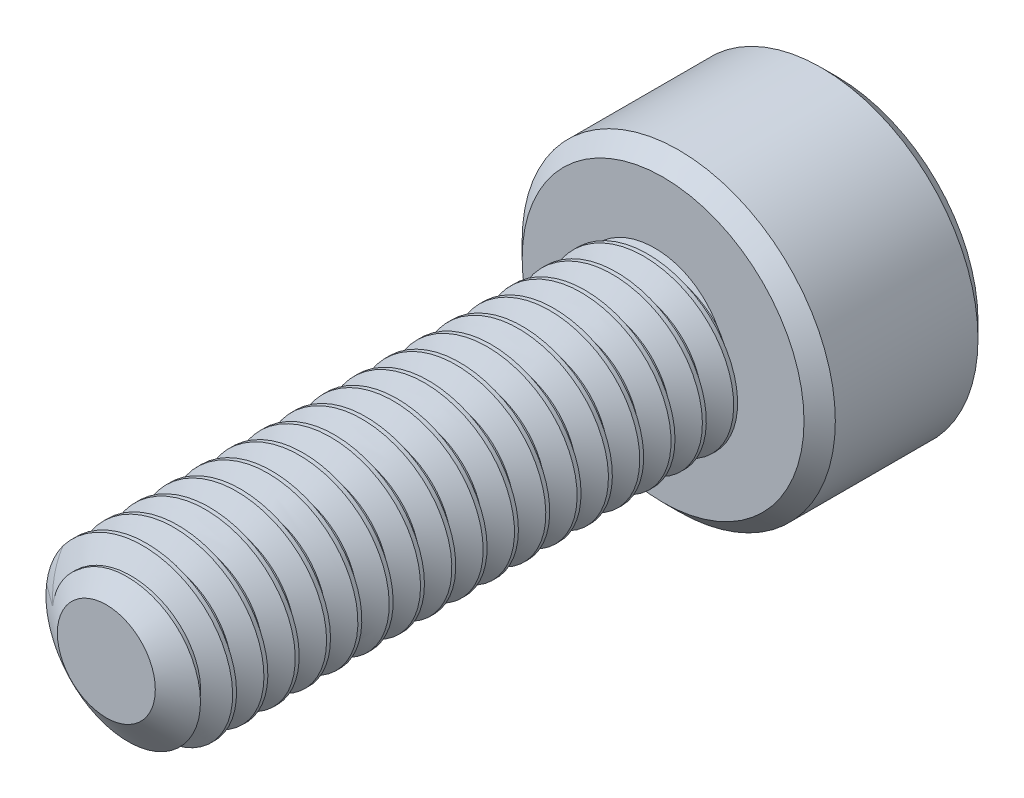
SolidWorks part; units mm, degrees
ref_plane "Front Plane" through (0, 0, 0) normal (0, 0, 1) x (1, 0, 0)
ref_plane "Top Plane" through (0, 0, 0) normal (0, 1, 0) x (1, 0, 0)
ref_plane "Right Plane" through (0, 0, 0) normal (1, 0, 0) x (0, 0, -1)
sketch "Sketch1" plane through (0, 0, 0) normal (0, 0, 1) x (1, 0, 0)
  circle A0 centre (0, 0) radius 1.25
  dimension "OD" = 2.5
extrude "Extrude1" add sketch "Sketch1" against normal blind 8
sketch "Sketch2" plane through (0, 0, 0) normal (0, 0, 1) x (1, 0, 0)
  circle A0 centre (0, 0) radius 1.25 construction
  circle A1 centre (0, 0) radius 1.25
curve "Helix/Spiral1" pitch 0.45 height 8.45 radius 1.25 centre (0, 0, 0) axis (0, 0, -1) start towards (0, 1, 0) parameters "pitch"=0.45
sketch "Sketch3" plane through (0, 0, 0) normal (1, 0, 0) x (0, 0, -1)
  line L0 (-0.3937, 1.25) -> (-0.225, 0.9577)
  line L1 (-0.225, 0.9577) -> (-0.1688, 0.9577)
  line L2 (-0.1688, 0.9577) -> (0, 1.25)
  line L3 (-0.3937, 1.25) -> (0, 1.25)
  line L4 (-0.1969, 1.25) -> (-0.1969, 0.9577) construction
  line L5 (-0.3094, 1.1039) -> (-0.0844, 1.1039) construction
  line L6 (0, 1.25) -> (0, -1.25) construction
  dimension "D1" = 0.0563
  dimension "D2" = 0.225
  dimension "D3" = 60
sweep "Cut-Sweep1" cut profiles "Sketch3" path "Helix/Spiral1" align with end faces yes
sketch "Sketch4" plane through (0, 0, 0) normal (1, 0, 0) x (0, 0, -1)
  line L0 (0.3825, 1.25) -> (0, 0.7037)
  line L1 (0, 0.7037) -> (0, 1.25)
  line L2 (0.3825, 1.25) -> (0, 1.25)
  line L3 (-0.3937, 1.25) -> (0, 1.25) construction
  line L4 (0, 0) -> (7.0209, 0) construction
  dimension "D1" = 55
  dimension "D2" = 0.254
revolve "Cut-Revolve1" cut sketch "Sketch4" angle 360 about L4
sketch "Sketch6" plane through (0, 0, -8) normal (0, 0, -1) x (-1, 0, 0)
  circle A0 centre (0, 0) radius 2.25
  dimension "head dia" = 4.5
extrude "Extrude2" add sketch "Sketch6" along normal blind 2.5
sketch "Sketch7" plane through (0, 0, -10.5) normal (0, 0, -1) x (-1, 0, 0)
  line L1 (0, 1.1547) -> (-1, 0.5774)
  line L2 (-1, 0.5774) -> (-1, -0.5774)
  line L3 (-1, -0.5774) -> (0, -1.1547)
  line L4 (0, -1.1547) -> (1, -0.5774)
  line L5 (1, -0.5774) -> (1, 0.5774)
  line L6 (1, 0.5774) -> (0, 1.1547)
  circle A0 centre (0, 0) radius 1 construction
  dimension "hex dia" = 2
extrude "Cut-Extrude1" cut sketch "Sketch7" against normal blind 1.5
sketch "Sketch8" plane through (0, 0, -10.5) normal (0, 0, -1) x (-1, 0, 0)
  circle A0 centre (0, 0) radius 1.1547
extrude "Cut-Extrude2" cut sketch "Sketch8" against normal through all draft 45
chamfer "Chamfer1" distance 0.225 angle 45 2 edges at (-2.25, 0, -10.5) (-2.25, 0, -8)
sketch "Sketch10" plane through (0, 0, -8) normal (0, 0, 1) x (1, 0, 0)
  circle A1 centre (0, 0) radius 1.25
  circle A2 centre (0, 0) radius 1.25
  dimension "D1" = 0
ref_plane "Plane1" through (0, 0, 0) normal (0, 0, 1) x (1, 0, 0)
extrude "partial thread" [suppressed] add sketch "Sketch10" along normal up to surface (8 mm away) separate body up to plane "Plane1"
chamfer "Chamfer2" [suppressed] distance 0.05 angle 45
combine bodies "Combine1" [suppressed] operation type add bodies to combine 107 108
sketch "Sketch9" plane through (0, 0, 0) normal (1, 0, 0) x (0, 0, -1)
  line L0 (0, 1.25) -> (0, -1.25) construction
  line L1 (1.125, 1.25) -> (1.125, -1.25) construction
  dimension "D1" = 1.125
equation "\"D3@Helix/Spiral1\" = \"screw length@Extrude1\"+\"pitch@Helix/Spiral1\""
equation "\"D1@Sketch3\" = \"pitch@Helix/Spiral1\"*.125"
equation "\"D2@Sketch3\" = \"pitch@Helix/Spiral1\"*.5"
equation "\"D1@Cut-Extrude1\" = \"hex dia@Sketch7\"*.75"
equation "\"D1@Chamfer1\" = \"head dia@Sketch6\"*.05"
equation "\"D1@Sketch9\" = \"pitch@Helix/Spiral1\"*2.5"
equation "\"D1@Chamfer2\"=\"OD@Sketch1\"*.02"
